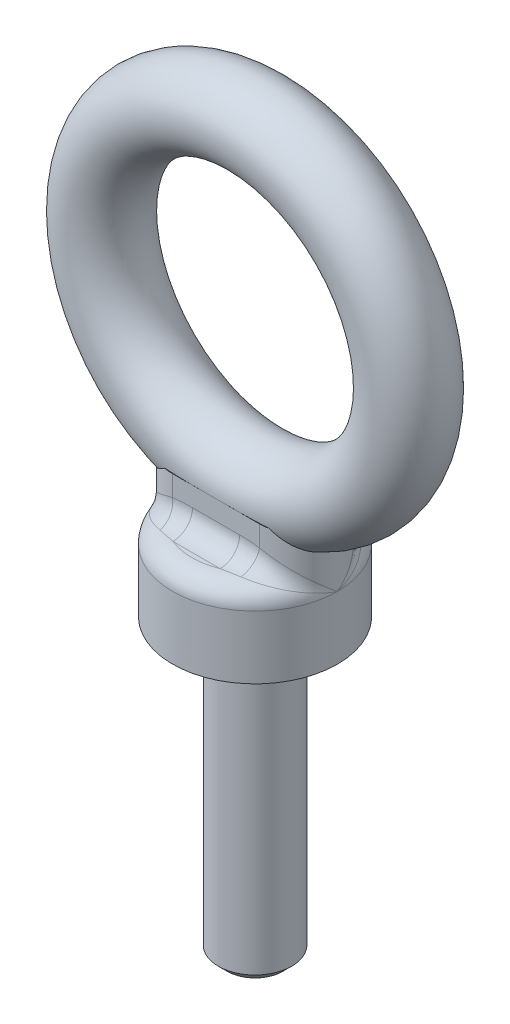
SolidWorks part; units mm, degrees
ref_plane "Front Plane" through (0, 0, 0) normal (0, 0, 1) x (1, 0, 0)
ref_plane "Top Plane" through (0, 0, 0) normal (0, 1, 0) x (1, 0, 0)
ref_plane "Right Plane" through (0, 0, 0) normal (1, 0, 0) x (0, 0, -1)
sketch "Sketch1" plane through (0, 0, 0) normal (0, 0, 1) x (1, 0, 0)
  line L0 (0, -32) -> (0, 0) construction
  line L1 (0, 0) -> (0, 9) construction
  line L2 (0, 9) -> (0, 17.5) construction
  line L3 (0, 17.5) -> (0, 42.5) construction
  line L4 (0, 42.5) -> (0, 51) construction
  line L5 (-4, -32) -> (4, -32) construction
  line L6 (-9, 0) -> (9, 0) construction
  line L7 (-4, 0) -> (4, 0) construction
  circle A0 centre (0, 30) radius 21 construction
  circle A1 centre (0, 30) radius 12.5 construction
  circle A2 centre (0, 46.75) radius 4.25 construction
  circle A3 centre (0, 13.25) radius 4.25 construction
  point P9 (0, 0)
sketch "Sketch2" plane through (0, 0, 0) normal (1, 0, 0) x (0, 0, -1)
  line L0 (-4.25, 30) -> (4.25, 30) construction
  line L1 (0, 51) -> (0, 42.5) construction
  line L2 (-4.25, 46.75) -> (4.25, 46.75) construction
  circle A0 centre (0, 46.75) radius 4.25
revolve "Revolve1" add sketch "Sketch2" angle 360 about L0
sketch "Sketch3" plane through (0, 0, 0) normal (0, 0, 1) x (1, 0, 0)
  line L0 (-9, 0) -> (0, 0)
  line L1 (0, 0) -> (0, 9)
  line L4 (-9, 0) -> (-9, 9)
  line L5 (0, 9) -> (-9, 9)
revolve "Revolve2" add sketch "Sketch3" angle 360 about L1
fillet "Fillet1" radius 2.125 1 edges at (9, 9, 0)
sketch "Sketch4" plane through (0, 0, 0) normal (0, 1, 0) x (1, 0, 0)
  line L0 (-4.75, 0) -> (4.75, 0) construction
  line L1 (-4.75, 4.25) -> (4.75, 4.25)
  line L2 (-4.75, -4.25) -> (4.75, -4.25)
  arc A0 (-4.75, 4.25) -> (-4.75, -4.25) centre (-4.75, 0) ccw
  arc A1 (4.75, -4.25) -> (4.75, 4.25) centre (4.75, 0) ccw
  circle A2 centre (0, 0) radius 9 construction
  point P2 (0, 0)
extrude "Boss-Extrude3" add sketch "Sketch4" along normal up to vertex (13.25 mm away) up to point (0, 13.25, 0)
fillet "Fillet2" radius 2.125 8 edges at (7.6883, 8.4703, 3.0707) (5.1007, 9, 4.2355) (-5.1007, 9, 4.2355) (0, 9, 4.25) (-7.6883, 8.4703, -3.0707) (-5.1007, 9, -4.2355) (5.1007, 9, -4.2355) (0, 9, -4.25)
sketch "Sketch5" plane through (0, 0, 0) normal (0, -1, 0) x (1, 0, 0)
  circle A0 centre (0, 0) radius 4
extrude "Boss-Extrude2" add sketch "Sketch5" along normal up to vertex (32 mm away) up to point (0, -32, 0)
ref_plane "Plane1" through (0, 0, 0) normal (0, -1, 0) x (1, 0, 0)
split "Split1" trim tools "Plane1" resulting bodies 105 106
sketch "Sketch6" plane through (0, -32, 0) normal (0, -1, 0) x (1, 0, 0)
  circle A1 centre (0, 0) radius 4
  circle A2 centre (0, 0) radius 4
  point P0 (4, 0)
  point P1 (0, -4)
  dimension "D1" = 0
sketch "Sketch7" plane through (0, 0, 0) normal (0, 0, 1) x (1, 0, 0)
  line L0 (4.1353, -31.9219) -> (4.1353, -33.1719) construction
  line L1 (4.1353, -33.1719) -> (3.0528, -32.5469) construction
  line L2 (3.0528, -32.5469) -> (4.1353, -31.9219) construction
  line L3 (3.1881, -32.4688) -> (3.1881, -32.625) construction
  line L4 (4, -32) -> (4, -33.0938) construction
  line L5 (3.0528, -32.5469) -> (3.1881, -32.5469) construction
  line L6 (4, -32.5469) -> (4.1353, -32.5469) construction
  line L7 (4.0677, -31.9609) -> (3.1881, -32.4688)
  line L8 (3.1881, -32.4688) -> (3.1881, -32.625)
  line L9 (3.1881, -32.625) -> (4.0677, -33.1328)
  line L10 (4.0677, -33.1328) -> (4.0677, -31.9609)
  point P13 (4.0677, -32.5469)
  dimension "D1" = 1.25
  dimension "D2" = 0.1562
sketch "Sketch8" plane through (0, -32, 0) normal (0, -1, 0) x (1, 0, 0)
  circle A0 centre (0, 0) radius 3.0528
extrude "Cut-Extrude1" cut sketch "Sketch8" against normal up to vertex (32 mm away) draft 45 flip side to cut up to point (0, 0, 0)
combine bodies "Combine1" operation type add bodies to combine 108 106
sketch "SketchY" plane through (0, 0, 0) normal (1, 0, 0) x (0, 0, -1)
  line L0 (4, -32) -> (4, -13.625) construction
  dimension "D1" = 18.375
equation "\"D1@Fillet1\"= \"Dia.@Sketch1\" / 4"
equation "\"D1@Fillet2\" = \"D1@Fillet1\""
equation "\"D2@Sketch7\" = \"D1@Sketch7\" / 8"
